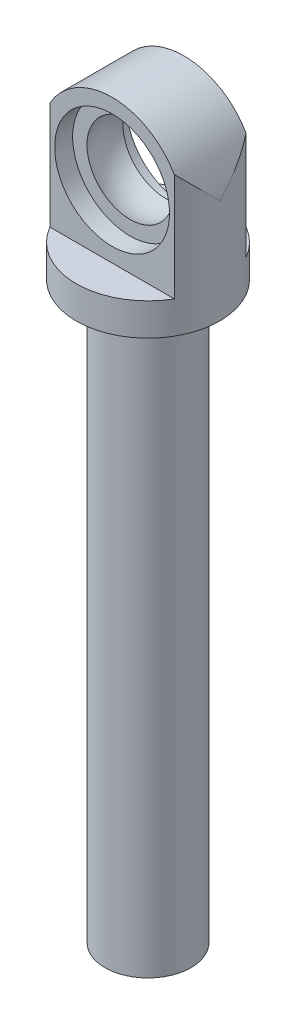
SolidWorks part; units mm, degrees
ref_plane "前视基准面" through (0, 0, 0) normal (0, 0, 1) x (1, 0, 0)
ref_plane "上视基准面" through (0, 0, 0) normal (0, 1, 0) x (1, 0, 0)
ref_plane "右视基准面" through (0, 0, 0) normal (1, 0, 0) x (0, 0, -1)
sketch "草图1" plane through (0, 0, 0) normal (0, 1, 0) x (1, 0, 0)
  circle A0 centre (0, 0) radius 10
  dimension "D1" = 20
extrude "凸台-拉伸1" add sketch "草图1" along normal blind 4.5
sketch "草图4" plane through (0, 0, 0) normal (0, 0, 1) x (1, 0, 0)
  line L0 (10, 4.5) -> (-10, 4.5) construction
  line L1 (-10, 4.5) -> (10, 4.5)
  line L2 (-10, 4.5) -> (-10, 14.5)
  line L4 (10, 4.5) -> (10, 14.5)
  line L5 (0, 193.283) -> (0, 138.3299) construction
  arc A0 (-10, 14.5) -> (10, 14.5) centre (0, 14.5) cw
  circle A1 centre (0, 14.5) radius 8
  dimension "D4" = 16
  dimension "D1" = 10
  dimension "D2" = 10
  dimension "D3" = 10
extrude "凸台-拉伸3" add sketch "草图4" against normal mid plane 10
sketch "草图5" plane through (0, 0, 0) normal (0, 0, 1) x (1, 0, 0)
  circle A0 centre (0, 14.5) radius 8
extrude "凸台-拉伸4" add sketch "草图5" along normal mid plane 5
ref_plane "基准面4" through (0, 0, 4.5) normal (0, 0, 1) x (1, 0, 0)
sketch "草图7" plane through (0, 0, 2.5) normal (0, 0, 1) x (1, 0, 0)
  circle A0 centre (0, 14.5) radius 6
  dimension "D1" = 12
sketch "草图8" plane through (0, 0, 4.5) normal (0, 0, 1) x (1, 0, 0)
  circle A0 centre (0, 14.5) radius 4
  dimension "D1" = 8
loft "放样1" add profiles "草图8", "草图7" connector at (0.1256, 18.498, 4.5) connector at (0.2826, 20.4933, 2.5)
mirror "镜向1" about plane through (0, 0, 0) normal (0, 0, 1) of "放样1"
sketch "草图9" plane through (0, 4.5, 0) normal (0, 1, 0) x (1, 0, 0)
  circle A0 centre (0, 0) radius 10
  circle A1 centre (0, 0) radius 14.6272
extrude "切除-拉伸1" cut sketch "草图9" along normal blind 18
sketch "草图10" plane through (0, 0, 4.5) normal (0, 0, 1) x (1, 0, 0)
  circle A0 centre (0, 14.5) radius 2.5
  dimension "D1" = 5
extrude "切除-拉伸2" cut sketch "草图10" against normal blind 10
sketch "草图2" plane through (0, 0, 0) normal (0, -1, 0) x (1, 0, 0)
  circle A0 centre (0, 0) radius 6
  dimension "D2" = 12
extrude "凸台-拉伸5" add sketch "草图2" along normal blind 80 contours A0
sketch "草图11" plane through (0, 0, 4.5) normal (0, 0, 1) x (1, 0, 0)
  circle A0 centre (0, 14.5) radius 6
extrude "切除-拉伸3" cut sketch "草图11" against normal blind 36
sketch "草图12" plane through (0, 0, 0) normal (0, 0, 1) x (1, 0, 0)
  line L0 (0, 8) -> (0, 21)
  arc A0 (0, 8) -> (0, 21) centre (0, 14.5) ccw
  dimension "D1" = 13
revolve "切除-旋转1" cut sketch "草图12" angle 360 about L0
